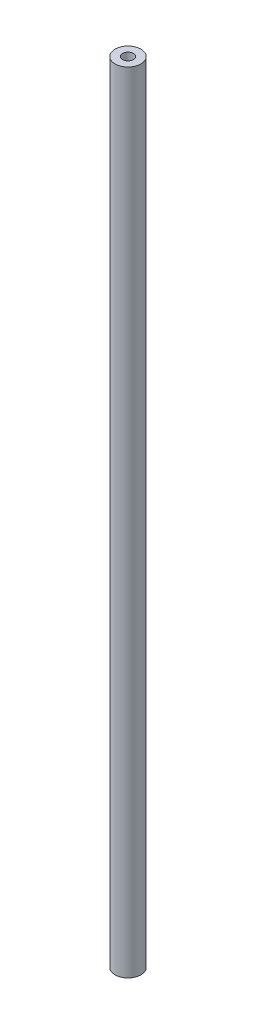
SolidWorks part; units mm, degrees
material "6063-T6"
ref_plane "Płaszczyzna przednia" through (0, 0, 0) normal (0, 0, 1) x (1, 0, 0)
ref_plane "Płaszczyzna górna" through (0, 0, 0) normal (0, 1, 0) x (1, 0, 0)
ref_plane "Płaszczyzna prawa" through (0, 0, 0) normal (1, 0, 0) x (0, 0, -1)
sketch "Szkic1" plane through (0, 0, 0) normal (0, 1, 0) x (1, 0, 0)
  circle A0 centre (0, 0) radius 5
  dimension "D1" = 10
extrude "Dodanie-wyciągnięcie1" add sketch "Szkic1" along normal blind 306
sketch "Szkic2" plane through (0, 0, 0) normal (0, -1, 0) x (-1, 0, 0)
  point P0 (0, 0)
hole_wizard "Tap Drill for M5 Tap2" positions "Szkic2" profile "Szkic3" hole size "M5" standard "DIN"
sketch "Szkic3" plane through (0, 0, 0) normal (1, 0, 0) x (0, 0, -1)
  line L0 (0, 0) -> (0, 31.2618)
  line L1 (0, 31.2618) -> (2.1, 30)
  line L2 (2.1, 30) -> (2.1, 0)
  line L5 (2.1, 0) -> (0, 0)
  line L10 (0, 31.2618) -> (-2.1, 30) construction
  line L11 (0, -6.35) -> (0, 107.95) construction
  dimension "Średnica otworu" = 4.2
  dimension "Głębokość otworu" = 30
  dimension "Kąt wiertła" = 118
sketch "Szkic4" plane through (0, 306, 0) normal (0, 1, 0) x (1, 0, 0)
  point P0 (0, 0)
hole_wizard "Tap Drill for M5 Tap1" positions "Szkic4" profile "Szkic5" hole size "M5" standard "DIN"
sketch "Szkic5" plane through (0, 306, 0) normal (1, 0, 0) x (0, 0, 1)
  line L0 (0, 0) -> (0, 31.2618)
  line L1 (0, 31.2618) -> (2.1, 30)
  line L2 (2.1, 30) -> (2.1, 0)
  line L5 (2.1, 0) -> (0, 0)
  line L10 (0, 31.2618) -> (-2.1, 30) construction
  line L11 (0, -6.35) -> (0, 107.95) construction
  dimension "Średnica otworu" = 4.2
  dimension "Głębokość otworu" = 30
  dimension "Kąt wiertła" = 118
